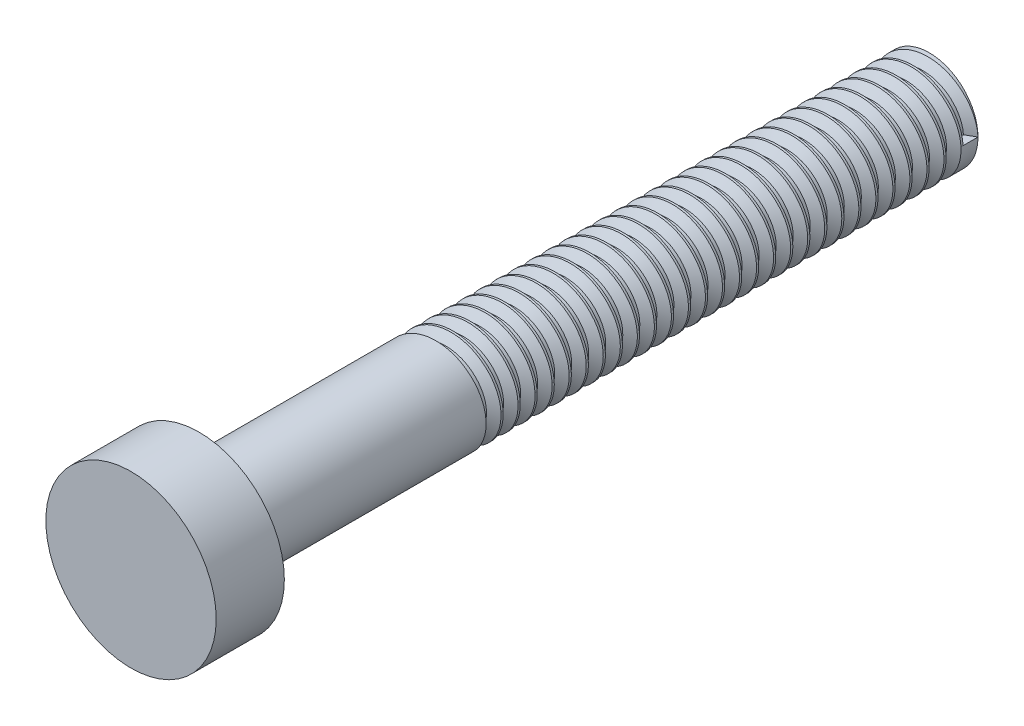
SolidWorks part; units mm, degrees
ref_plane "Front Plane" through (0, 0, 0) normal (0, 0, 1) x (1, 0, 0)
ref_plane "Top Plane" through (0, 0, 0) normal (0, 1, 0) x (1, 0, 0)
ref_plane "Right Plane" through (0, 0, 0) normal (1, 0, 0) x (0, 0, -1)
sketch "Sketch1" plane through (0, 0, 0) normal (0, 0, 1) x (1, 0, 0)
  circle A0 centre (0, 0) radius 2
  dimension "D1" = 4
extrude "Boss-Extrude1" add sketch "Sketch1" against normal blind 30
sketch "Sketch2" plane through (0, 0, 0) normal (0, 0, 1) x (1, 0, 0)
  circle A0 centre (0, 0) radius 3.5
  dimension "D1" = 7
extrude "Boss-Extrude2" add sketch "Sketch2" along normal blind 2.8
thread "Thread1" pitch 0.7 method cut profile "Thread Profile1" start angle 0, offset 0, length 20, pitch 0.7, diameter 4
ref_plane "Plane1" through (2, 0, -30) normal (0, -1, 0) x (1, 0, 0)
sketch "Thread Profile1" plane through (2, 0, -30) normal (0, -1, 0) x (1, 0, 0)
  line L0 (0, 0) -> (0, 0.7) construction
  line L11 (0, 0) -> (0, 0.6125)
  line L12 (0, 0.6125) -> (-0.3789, 0.3937)
  line L13 (-0.3789, 0.3937) -> (-0.3789, 0.2187)
  line L15 (-0.3789, 0.2187) -> (0, 0)
  line L17 (-0.3789, 0.3062) -> (0, 0.3062) construction
  point P2 (0, 0)
  dimension "Pitch" = 0.7
  dimension "Profile_Angle" = 60
  dimension "Profile_Land" = 0.175
  dimension "Profile_Height" = 0.3789
